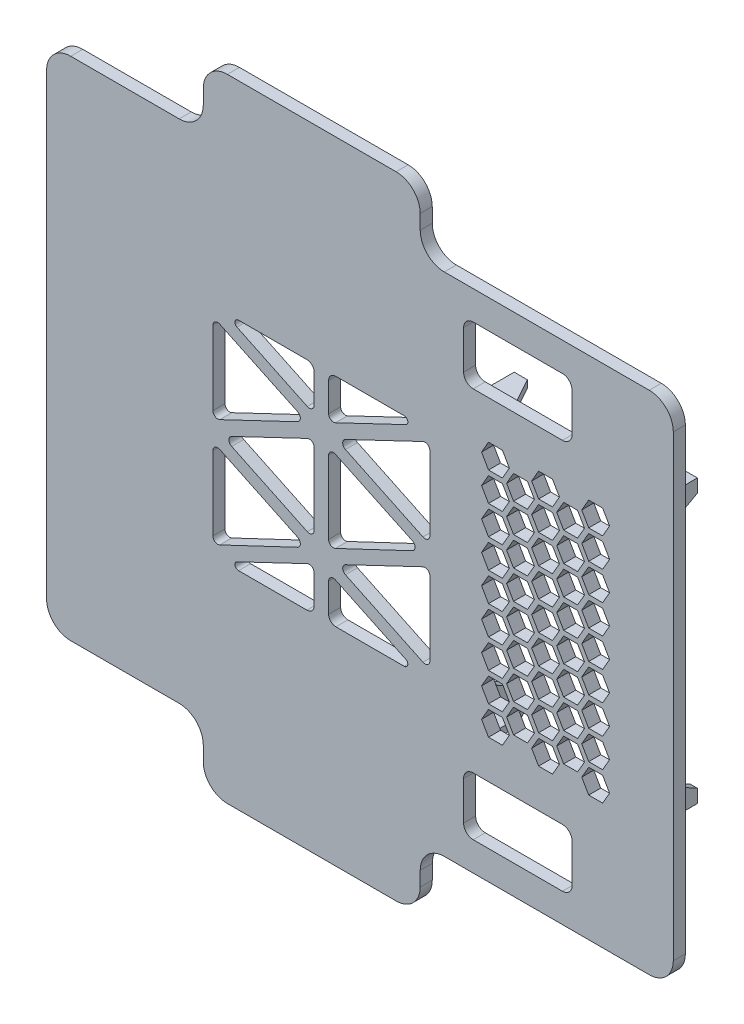
SolidWorks part; units mm, degrees
ref_plane "前视基准面" through (0, 0, 0) normal (0, 0, 1) x (1, 0, 0)
ref_plane "上视基准面" through (0, 0, 0) normal (0, 1, 0) x (1, 0, 0)
ref_plane "右视基准面" through (0, 0, 0) normal (1, 0, 0) x (0, 0, -1)
sketch "草图1" plane through (0, 0, 0) normal (0, 0, 1) x (1, 0, 0)
  line L2 (-130, 95) -> (-130, -95)
  line L3 (-120, -105) -> (-75, -105)
  line L4 (130, 95) -> (130, -95)
  line L5 (126.7518, 102.3765) -> (130, 105) construction
  line L6 (-130, -105) -> (-126.7518, -102.3765) construction
  line L9 (-65, -115) -> (-65, -121)
  line L10 (-55, -131) -> (15, -131)
  line L11 (25, -121) -> (25, -115)
  line L13 (35, -105) -> (120, -105)
  line L14 (126.7518, -102.3765) -> (130, -105) construction
  line L15 (-130, 105) -> (-126.7518, 102.3765) construction
  line L16 (-130, 0) -> (130, 0) construction
  line L17 (35, 105) -> (120, 105)
  line L18 (25, 121) -> (25, 115)
  line L19 (-55, 131) -> (15, 131)
  line L20 (-65, 115) -> (-65, 121)
  line L21 (-120, 105) -> (-75, 105)
  arc A1 (-120, -105) -> (-130, -95) centre (-120, -95) cw
  arc A3 (120, -105) -> (130, -95) centre (120, -95) ccw
  arc A8 (-65, -115) -> (-75, -105) centre (-75, -115) ccw
  arc A9 (25, -115) -> (35, -105) centre (35, -115) cw
  arc A10 (-55, -131) -> (-65, -121) centre (-55, -121) cw
  arc A11 (15, -131) -> (25, -121) centre (15, -121) ccw
  arc A12 (15, 131) -> (25, 121) centre (15, 121) cw
  arc A13 (-55, 131) -> (-65, 121) centre (-55, 121) ccw
  arc A14 (25, 115) -> (35, 105) centre (35, 115) ccw
  arc A15 (-65, 115) -> (-75, 105) centre (-75, 115) cw
  arc A16 (120, 105) -> (130, 95) centre (120, 95) cw
  arc A17 (-120, 105) -> (-130, 95) centre (-120, 95) ccw
  point P0 (0, 0)
  point P40 (25, -105)
  point P45 (25, 105)
  dimension "D2" = 10
  dimension "D3" = 65
  dimension "D4" = 10
  dimension "D5" = 105
  dimension "D7" = 10
  dimension "D8" = 10
  dimension "D10" = 10
  dimension "D12" = 10
  dimension "D13" = 105
  dimension "D18" = 90
  dimension "D19" = 6
extrude "凸台-拉伸1" add sketch "草图1" along normal blind 5
sketch "草图4" plane through (0, 0, 0) normal (0, 0, -1) x (-1, 0, 0)
  line L0 (-39, -47.5) -> (-39, -58.5)
  line L1 (-39, -58.5) -> (-50, -58.5)
  line L2 (-50, -58.5) -> (-50, -55.5)
  line L3 (-50, -55.5) -> (-42, -55.5)
  line L4 (-42, -55.5) -> (-42, -47.5)
  line L5 (-42, -47.5) -> (-39, -47.5)
  line L6 (-130, 0) -> (-25.5592, 0) construction
  line L7 (-130, -95) -> (-130, 95) construction
  line L10 (-130, -95) -> (-130, 95) construction
  dimension "D1" = 11
  dimension "D2" = 11
  dimension "D3" = 3
  dimension "D4" = 3
  dimension "D5" = 80
  dimension "D7" = 55.5
extrude "凸台-拉伸2" add sketch "草图4" along normal blind 20
sketch "草图5" plane through (0, -58.5, 0) normal (0, -1, 0) x (1, 0, 0)
  line L0 (50, -10) -> (44.5, -20)
  line L1 (50, -20) -> (50, 0) construction
  line L2 (50, -20) -> (39, -20) construction
  line L3 (44.5, -20) -> (50, -20)
  line L4 (50, -20) -> (50, -10)
  dimension "D1" = 10
  dimension "D2" = 5.5
extrude "切除-拉伸3" cut sketch "草图5" against normal blind 10
sketch "草图6" plane through (39, 0, 0) normal (-1, 0, 0) x (0, 0, 1)
  line L0 (-20, -53) -> (-10, -47.5)
  line L1 (-20, -58.5) -> (-20, -47.5) construction
  line L2 (-20, -47.5) -> (0, -47.5) construction
  line L3 (-10, -47.5) -> (-20, -47.5)
  line L4 (-20, -47.5) -> (-20, -53)
  dimension "D1" = 10
  dimension "D2" = 5.5
extrude "切除-拉伸4" cut sketch "草图6" against normal blind 10
ref_plane "基准面2" through (77, 0, 0) normal (1, 0, 0) x (0, 0, -1)
mirror "镜向1" about plane through (77, 0, 0) normal (1, 0, 0) of "凸台-拉伸2", "切除-拉伸4", "切除-拉伸3"
mirror "镜向2" about plane through (0, 0, 0) normal (0, 1, 0) of "镜向1"
sketch "草图7" plane through (0, 0, 0) normal (0, 0, -1) x (-1, 0, 0)
  line L4 (-112, -55.5) -> (-104, -55.5) construction
  line L5 (-112, 47.5) -> (-112, 55.5) construction
  line L6 (-112, 55.5) -> (-104, 55.5) construction
  line L7 (-92.013, 36) -> (-94.8997, 41)
  line L8 (-94.8997, 41) -> (-100.6732, 41)
  line L9 (-100.6732, 41) -> (-103.56, 36)
  line L10 (-103.56, 36) -> (-100.6732, 31)
  line L11 (-100.6732, 31) -> (-94.8997, 31)
  line L12 (-94.8997, 31) -> (-92.013, 36)
  line L13 (-77.0019, 36) -> (-97.7865, 36) construction
  line L14 (-74.1151, 31) -> (-71.2284, 36)
  line L15 (-71.2284, 36) -> (-74.1151, 41)
  line L16 (-74.1151, 41) -> (-79.8886, 41)
  line L17 (-79.8886, 41) -> (-82.7754, 36)
  line L18 (-82.7754, 36) -> (-79.8886, 31)
  line L19 (-79.8886, 31) -> (-74.1151, 31)
  line L20 (-92.013, 24) -> (-94.8997, 29)
  line L21 (-93.1677, 30) -> (-90.2809, 25)
  line L22 (-90.2809, 25) -> (-84.5074, 25)
  line L23 (-84.5074, 25) -> (-81.6207, 30)
  line L24 (-81.6207, 30) -> (-84.5074, 35)
  line L25 (-84.5074, 35) -> (-90.2809, 35)
  line L26 (-90.2809, 35) -> (-93.1677, 30)
  line L27 (-84.5074, 37) -> (-81.6207, 42)
  line L28 (-81.6207, 42) -> (-84.5074, 47)
  line L29 (-84.5074, 47) -> (-90.2809, 47)
  line L30 (-90.2809, 47) -> (-93.1677, 42)
  line L31 (-93.1677, 42) -> (-90.2809, 37)
  line L32 (-90.2809, 37) -> (-84.5074, 37)
  line L33 (-79.8886, 43) -> (-74.1151, 43)
  line L34 (-74.1151, 43) -> (-71.2284, 48)
  line L35 (-71.2284, 48) -> (-74.1151, 53)
  line L36 (-74.1151, 53) -> (-79.8886, 53)
  line L37 (-79.8886, 53) -> (-82.7754, 48)
  line L38 (-82.7754, 48) -> (-79.8886, 43)
  line L39 (-94.8997, 43) -> (-92.013, 48)
  line L40 (-92.013, 48) -> (-94.8997, 53)
  line L41 (-94.8997, 53) -> (-100.6732, 53)
  line L42 (-100.6732, 53) -> (-103.56, 48)
  line L43 (-103.56, 48) -> (-100.6732, 43)
  line L44 (-100.6732, 43) -> (-94.8997, 43)
  line L45 (-72.3831, 42) -> (-69.4963, 37)
  line L46 (-69.4963, 37) -> (-63.7228, 37)
  line L47 (-63.7228, 37) -> (-60.8361, 42)
  line L48 (-60.8361, 42) -> (-63.7228, 47)
  line L49 (-63.7228, 47) -> (-69.4963, 47)
  line L50 (-69.4963, 47) -> (-72.3831, 42)
  line L51 (-94.8997, 29) -> (-100.6732, 29)
  line L52 (-100.6732, 29) -> (-103.56, 24)
  line L53 (-103.56, 24) -> (-100.6732, 19)
  line L54 (-100.6732, 19) -> (-94.8997, 19)
  line L55 (-94.8997, 19) -> (-92.013, 24)
  line L56 (-93.1677, 18) -> (-90.2809, 13)
  line L57 (-90.2809, 13) -> (-84.5074, 13)
  line L58 (-84.5074, 13) -> (-81.6207, 18)
  line L59 (-81.6207, 18) -> (-84.5074, 23)
  line L60 (-84.5074, 23) -> (-90.2809, 23)
  line L61 (-90.2809, 23) -> (-93.1677, 18)
  line L62 (-74.1151, 19) -> (-71.2284, 24)
  line L63 (-71.2284, 24) -> (-74.1151, 29)
  line L64 (-74.1151, 29) -> (-79.8886, 29)
  line L65 (-79.8886, 29) -> (-82.7754, 24)
  line L66 (-82.7754, 24) -> (-79.8886, 19)
  line L67 (-79.8886, 19) -> (-74.1151, 19)
  line L68 (-72.3831, 30) -> (-69.4963, 25)
  line L69 (-69.4963, 25) -> (-63.7228, 25)
  line L70 (-63.7228, 25) -> (-60.8361, 30)
  line L71 (-60.8361, 30) -> (-63.7228, 35)
  line L72 (-63.7228, 35) -> (-69.4963, 35)
  line L73 (-69.4963, 35) -> (-72.3831, 30)
  line L74 (-92.013, 12) -> (-94.8997, 17)
  line L75 (-94.8997, 17) -> (-100.6732, 17)
  line L76 (-100.6732, 17) -> (-103.56, 12)
  line L77 (-103.56, 12) -> (-100.6732, 7)
  line L78 (-100.6732, 7) -> (-94.8997, 7)
  line L79 (-94.8997, 7) -> (-92.013, 12)
  line L80 (-93.1677, 6) -> (-90.2809, 1)
  line L81 (-90.2809, 1) -> (-84.5074, 1)
  line L82 (-84.5074, 1) -> (-81.6207, 6)
  line L83 (-81.6207, 6) -> (-84.5074, 11)
  line L84 (-84.5074, 11) -> (-90.2809, 11)
  line L85 (-90.2809, 11) -> (-93.1677, 6)
  line L86 (-74.1151, 7) -> (-71.2284, 12)
  line L87 (-71.2284, 12) -> (-74.1151, 17)
  line L88 (-74.1151, 17) -> (-79.8886, 17)
  line L89 (-79.8886, 17) -> (-82.7754, 12)
  line L90 (-82.7754, 12) -> (-79.8886, 7)
  line L91 (-79.8886, 7) -> (-74.1151, 7)
  line L92 (-72.3831, 18) -> (-69.4963, 13)
  line L93 (-69.4963, 13) -> (-63.7228, 13)
  line L94 (-63.7228, 13) -> (-60.8361, 18)
  line L95 (-60.8361, 18) -> (-63.7228, 23)
  line L96 (-63.7228, 23) -> (-69.4963, 23)
  line L97 (-69.4963, 23) -> (-72.3831, 18)
  line L98 (-92.013, 0) -> (-94.8997, 5)
  line L99 (-94.8997, 5) -> (-100.6732, 5)
  line L100 (-100.6732, 5) -> (-103.56, 0)
  line L101 (-103.56, 0) -> (-100.6732, -5)
  line L102 (-100.6732, -5) -> (-94.8997, -5)
  line L103 (-94.8997, -5) -> (-92.013, 0)
  line L104 (-93.1677, -6) -> (-90.2809, -11)
  line L105 (-90.2809, -11) -> (-84.5074, -11)
  line L106 (-84.5074, -11) -> (-81.6207, -6)
  line L107 (-81.6207, -6) -> (-84.5074, -1)
  line L108 (-84.5074, -1) -> (-90.2809, -1)
  line L109 (-90.2809, -1) -> (-93.1677, -6)
  line L110 (-74.1151, -5) -> (-71.2284, 0)
  line L111 (-71.2284, 0) -> (-74.1151, 5)
  line L112 (-74.1151, 5) -> (-79.8886, 5)
  line L113 (-79.8886, 5) -> (-82.7754, 0)
  line L114 (-82.7754, 0) -> (-79.8886, -5)
  line L115 (-79.8886, -5) -> (-74.1151, -5)
  line L116 (-72.3831, 6) -> (-69.4963, 1)
  line L117 (-69.4963, 1) -> (-63.7228, 1)
  line L118 (-63.7228, 1) -> (-60.8361, 6)
  line L119 (-60.8361, 6) -> (-63.7228, 11)
  line L120 (-63.7228, 11) -> (-69.4963, 11)
  line L121 (-69.4963, 11) -> (-72.3831, 6)
  line L122 (-92.013, -12) -> (-94.8997, -7)
  line L123 (-94.8997, -7) -> (-100.6732, -7)
  line L124 (-100.6732, -7) -> (-103.56, -12)
  line L125 (-103.56, -12) -> (-100.6732, -17)
  line L126 (-100.6732, -17) -> (-94.8997, -17)
  line L127 (-94.8997, -17) -> (-92.013, -12)
  line L128 (-93.1677, -18) -> (-90.2809, -23)
  line L129 (-90.2809, -23) -> (-84.5074, -23)
  line L130 (-84.5074, -23) -> (-81.6207, -18)
  line L131 (-81.6207, -18) -> (-84.5074, -13)
  line L132 (-84.5074, -13) -> (-90.2809, -13)
  line L133 (-90.2809, -13) -> (-93.1677, -18)
  line L134 (-74.1151, -17) -> (-71.2284, -12)
  line L135 (-71.2284, -12) -> (-74.1151, -7)
  line L136 (-74.1151, -7) -> (-79.8886, -7)
  line L137 (-79.8886, -7) -> (-82.7754, -12)
  line L138 (-82.7754, -12) -> (-79.8886, -17)
  line L139 (-79.8886, -17) -> (-74.1151, -17)
  line L140 (-72.3831, -6) -> (-69.4963, -11)
  line L141 (-69.4963, -11) -> (-63.7228, -11)
  line L142 (-63.7228, -11) -> (-60.8361, -6)
  line L143 (-60.8361, -6) -> (-63.7228, -1)
  line L144 (-63.7228, -1) -> (-69.4963, -1)
  line L145 (-69.4963, -1) -> (-72.3831, -6)
  line L146 (-92.013, -24) -> (-94.8997, -19)
  line L147 (-94.8997, -19) -> (-100.6732, -19)
  line L148 (-100.6732, -19) -> (-103.56, -24)
  line L149 (-103.56, -24) -> (-100.6732, -29)
  line L150 (-100.6732, -29) -> (-94.8997, -29)
  line L151 (-94.8997, -29) -> (-92.013, -24)
  line L152 (-93.1677, -30) -> (-90.2809, -35)
  line L153 (-90.2809, -35) -> (-84.5074, -35)
  line L154 (-84.5074, -35) -> (-81.6207, -30)
  line L155 (-81.6207, -30) -> (-84.5074, -25)
  line L156 (-84.5074, -25) -> (-90.2809, -25)
  line L157 (-90.2809, -25) -> (-93.1677, -30)
  line L158 (-74.1151, -29) -> (-71.2284, -24)
  line L159 (-71.2284, -24) -> (-74.1151, -19)
  line L160 (-74.1151, -19) -> (-79.8886, -19)
  line L161 (-79.8886, -19) -> (-82.7754, -24)
  line L162 (-82.7754, -24) -> (-79.8886, -29)
  line L163 (-79.8886, -29) -> (-74.1151, -29)
  line L164 (-72.3831, -18) -> (-69.4963, -23)
  line L165 (-69.4963, -23) -> (-63.7228, -23)
  line L166 (-63.7228, -23) -> (-60.8361, -18)
  line L167 (-60.8361, -18) -> (-63.7228, -13)
  line L168 (-63.7228, -13) -> (-69.4963, -13)
  line L169 (-69.4963, -13) -> (-72.3831, -18)
  line L170 (-92.013, -36) -> (-94.8997, -31)
  line L171 (-94.8997, -31) -> (-100.6732, -31)
  line L172 (-100.6732, -31) -> (-103.56, -36)
  line L173 (-103.56, -36) -> (-100.6732, -41)
  line L174 (-100.6732, -41) -> (-94.8997, -41)
  line L175 (-94.8997, -41) -> (-92.013, -36)
  line L176 (-93.1677, -42) -> (-90.2809, -47)
  line L177 (-90.2809, -47) -> (-84.5074, -47)
  line L178 (-84.5074, -47) -> (-81.6207, -42)
  line L179 (-81.6207, -42) -> (-84.5074, -37)
  line L180 (-84.5074, -37) -> (-90.2809, -37)
  line L181 (-90.2809, -37) -> (-93.1677, -42)
  line L182 (-74.1151, -41) -> (-71.2284, -36)
  line L183 (-71.2284, -36) -> (-74.1151, -31)
  line L184 (-74.1151, -31) -> (-79.8886, -31)
  line L185 (-79.8886, -31) -> (-82.7754, -36)
  line L186 (-82.7754, -36) -> (-79.8886, -41)
  line L187 (-79.8886, -41) -> (-74.1151, -41)
  line L188 (-72.3831, -30) -> (-69.4963, -35)
  line L189 (-69.4963, -35) -> (-63.7228, -35)
  line L190 (-63.7228, -35) -> (-60.8361, -30)
  line L191 (-60.8361, -30) -> (-63.7228, -25)
  line L192 (-63.7228, -25) -> (-69.4963, -25)
  line L193 (-69.4963, -25) -> (-72.3831, -30)
  line L194 (-92.013, -48) -> (-94.8997, -43)
  line L195 (-94.8997, -43) -> (-100.6732, -43)
  line L196 (-100.6732, -43) -> (-103.56, -48)
  line L197 (-103.56, -48) -> (-100.6732, -53)
  line L198 (-100.6732, -53) -> (-94.8997, -53)
  line L199 (-94.8997, -53) -> (-92.013, -48)
  line L206 (-74.1151, -53) -> (-71.2284, -48)
  line L207 (-71.2284, -48) -> (-74.1151, -43)
  line L208 (-74.1151, -43) -> (-79.8886, -43)
  line L209 (-79.8886, -43) -> (-82.7754, -48)
  line L210 (-82.7754, -48) -> (-79.8886, -53)
  line L211 (-79.8886, -53) -> (-74.1151, -53)
  line L212 (-72.3831, -42) -> (-69.4963, -47)
  line L213 (-69.4963, -47) -> (-63.7228, -47)
  line L214 (-63.7228, -47) -> (-60.8361, -42)
  line L215 (-60.8361, -42) -> (-63.7228, -37)
  line L216 (-63.7228, -37) -> (-69.4963, -37)
  line L217 (-69.4963, -37) -> (-72.3831, -42)
  line L218 (-61.9908, 36) -> (-59.104, 31)
  line L219 (-61.9908, 48) -> (-59.104, 43)
  line L220 (-59.104, 43) -> (-53.3305, 43)
  line L221 (-53.3305, 43) -> (-50.4438, 48)
  line L222 (-50.4438, 48) -> (-53.3305, 53)
  line L223 (-53.3305, 53) -> (-59.104, 53)
  line L224 (-59.104, 53) -> (-61.9908, 48)
  line L225 (-59.104, 31) -> (-53.3305, 31)
  line L226 (-53.3305, 31) -> (-50.4438, 36)
  line L227 (-50.4438, 36) -> (-53.3305, 41)
  line L228 (-53.3305, 41) -> (-59.104, 41)
  line L229 (-59.104, 41) -> (-61.9908, 36)
  line L230 (-61.9908, 24) -> (-59.104, 19)
  line L231 (-59.104, 19) -> (-53.3305, 19)
  line L232 (-53.3305, 19) -> (-50.4438, 24)
  line L233 (-50.4438, 24) -> (-53.3305, 29)
  line L234 (-53.3305, 29) -> (-59.104, 29)
  line L235 (-59.104, 29) -> (-61.9908, 24)
  line L236 (-61.9908, 12) -> (-59.104, 7)
  line L237 (-59.104, 7) -> (-53.3305, 7)
  line L238 (-53.3305, 7) -> (-50.4438, 12)
  line L239 (-50.4438, 12) -> (-53.3305, 17)
  line L240 (-53.3305, 17) -> (-59.104, 17)
  line L241 (-59.104, 17) -> (-61.9908, 12)
  line L242 (-61.9908, 0) -> (-59.104, -5)
  line L243 (-59.104, -5) -> (-53.3305, -5)
  line L244 (-53.3305, -5) -> (-50.4438, 0)
  line L245 (-50.4438, 0) -> (-53.3305, 5)
  line L246 (-53.3305, 5) -> (-59.104, 5)
  line L247 (-59.104, 5) -> (-61.9908, 0)
  line L248 (-61.9908, -12) -> (-59.104, -17)
  line L249 (-59.104, -17) -> (-53.3305, -17)
  line L250 (-53.3305, -17) -> (-50.4438, -12)
  line L251 (-50.4438, -12) -> (-53.3305, -7)
  line L252 (-53.3305, -7) -> (-59.104, -7)
  line L253 (-59.104, -7) -> (-61.9908, -12)
  line L254 (-61.9908, -24) -> (-59.104, -29)
  line L255 (-59.104, -29) -> (-53.3305, -29)
  line L256 (-53.3305, -29) -> (-50.4438, -24)
  line L257 (-50.4438, -24) -> (-53.3305, -19)
  line L258 (-53.3305, -19) -> (-59.104, -19)
  line L259 (-59.104, -19) -> (-61.9908, -24)
  line L260 (-61.9908, -36) -> (-59.104, -41)
  line L261 (-59.104, -41) -> (-53.3305, -41)
  line L262 (-53.3305, -41) -> (-50.4438, -36)
  line L263 (-50.4438, -36) -> (-53.3305, -31)
  line L264 (-53.3305, -31) -> (-59.104, -31)
  line L265 (-59.104, -31) -> (-61.9908, -36)
  line L266 (-61.9908, -48) -> (-59.104, -53)
  line L267 (-59.104, -53) -> (-53.3305, -53)
  line L268 (-53.3305, -53) -> (-50.4438, -48)
  line L269 (-50.4438, -48) -> (-53.3305, -43)
  line L270 (-53.3305, -43) -> (-59.104, -43)
  line L271 (-59.104, -43) -> (-61.9908, -48)
  line L272 (-93.1677, -54) -> (-90.2809, -59) [skipped]
  line L273 (-90.2809, -59) -> (-84.5074, -59) [skipped]
  line L274 (-84.5074, -59) -> (-81.6207, -54) [skipped]
  line L275 (-81.6207, -54) -> (-84.5074, -49) [skipped]
  line L276 (-84.5074, -49) -> (-90.2809, -49) [skipped]
  line L277 (-90.2809, -49) -> (-93.1677, -54) [skipped]
  circle A0 centre (-97.7865, 36) radius 5 construction
  circle A1 centre (-77.0019, 36) radius 5 construction
  circle A2 centre (-87.3942, 30) radius 5 construction
  circle A3 centre (-87.3942, 42) radius 5 construction
  circle A4 centre (-77.0019, 48) radius 5 construction
  circle A5 centre (-97.7865, 48) radius 5 construction
  circle A6 centre (-66.6096, 42) radius 5 construction
  circle A7 centre (-56.2173, 48) radius 5 construction
  point P4 (-87.3942, 37)
  dimension "D1" = 2
  dimension "D3" = 10
  dimension "D4" = 10
  dimension "D5" = 2
  dimension "D7" = 10
  dimension "D11" = 10
  dimension "D14" = 10
  dimension "D15" = 10
  dimension "D20" = 10
  dimension "D2" = 2
  dimension "D6" = 2
  dimension "D8" = 2
  dimension "D9" = 2
  dimension "D10" = 2
  dimension "D12" = 2
  dimension "D13" = 2
  dimension "D16" = 2
  dimension "D17" = 2
  dimension "D19" = 2
  dimension "D21" = 9
  dimension "D22" = 2.5
  dimension "D23" = 2.5
  dimension "D24" = 8.44
  dimension "D18" = 8
extrude "切除-拉伸5" cut sketch "草图7" against normal blind 5
sketch "草图8" plane through (0, 0, 0) normal (0, 0, -1) x (-1, 0, 0)
  line L0 (-75.3677, 120) -> (-75.3677, -120)
  line L1 (-100.0285, 77.2863) -> (-100.0285, -77.2863)
  line L2 (-100.0285, 77.2863) -> (-75.3677, 120)
  line L3 (-100.0285, -77.2863) -> (-75.3677, -120)
  line L4 (-37.1297, 0) -> (-146.8562, 0) construction
  dimension "D1" = 30
  dimension "D2" = 30
  dimension "D3" = 120
  dimension "D4" = 120
sketch "草图9" plane through (0, 0, 0) normal (0, 0, -1) x (-1, 0, 0)
  line L0 (148.8518, 0) -> (-37.1297, 0) construction
  line L1 (-29, 41) -> (-29, 4)
  line L2 (-25, -45) -> (13, -45)
  line L3 (61, -41) -> (61, -4)
  line L4 (57, 45) -> (19, 45)
  line L14 (-29, 41) -> (9.8049, 22.5)
  line L15 (57, 0) -> (19, -18.1163)
  line L16 (130, 95) -> (130, -95) construction
  line L17 (63, 93) -> (118, 93)
  line L18 (63, 93) -> (63, 66)
  line L19 (63, 66) -> (118, 66)
  line L20 (118, 93) -> (118, 66)
  line L21 (75, 105) -> (120, 105) construction
  line L22 (63, -66) -> (118, -66)
  line L23 (118, -93) -> (118, -66)
  line L24 (63, -93) -> (118, -93)
  line L25 (63, -93) -> (63, -66)
  line L26 (-120, 105) -> (-35, 105) construction
  line L27 (-43, 93) -> (-88, 93)
  line L28 (-43, 93) -> (-43, 69)
  line L29 (-43, 69) -> (-88, 69)
  line L30 (-88, 93) -> (-88, 69)
  line L31 (-130, -95) -> (-130, 95) construction
  line L32 (-43, -69) -> (-88, -69)
  line L33 (-88, -93) -> (-88, -69)
  line L34 (-43, -93) -> (-88, -93)
  line L35 (-43, -93) -> (-43, -69)
  line L36 (-25, 45) -> (13, 26.8837)
  line L37 (-25, -45) -> (13, -26.8837)
  line L38 (61, 41) -> (22.0746, 22.5575)
  line L39 (-25.5359, 0) -> (13, -18.258)
  line L40 (57, 45) -> (19, 26.8837)
  line L41 (57, -45) -> (19, -26.8837)
  line L42 (16, 61.4977) -> (16, -60.5731) construction
  line L43 (13, 45) -> (13, 26.8837)
  line L44 (19, 45) -> (19, 26.8837)
  line L45 (13, 18.258) -> (13, -18.258)
  line L46 (9.8049, 22.5) -> (-29, 4)
  line L47 (19, 18.1163) -> (57, 0)
  line L48 (22.0746, 22.5575) -> (61, 4)
  line L49 (13, 18.258) -> (-25.5359, 0)
  line L50 (19, 18.1163) -> (19, -18.1163)
  line L51 (22.0746, -22.5575) -> (61, -41)
  line L52 (9.8049, -22.5) -> (-29, -41)
  line L53 (9.8049, -22.5) -> (-29, -4)
  line L54 (22.0746, -22.5575) -> (61, -4)
  line L55 (13, -26.8837) -> (13, -45)
  line L56 (19, -26.8837) -> (19, -45)
  line L57 (13, 45) -> (-25, 45)
  line L58 (-29, -4) -> (-29, -41)
  line L59 (19, -45) -> (57, -45)
  line L60 (61, 4) -> (61, 41)
  line L61 (-44, 41) -> (-44, -37.8122) construction
  dimension "D1" = 45
  dimension "D2" = 45
  dimension "D3" = 15
  dimension "D4" = 90
  dimension "D5" = 1
  dimension "D7" = 12
  dimension "D8" = 12
  dimension "D9" = 27
  dimension "D10" = 55
  dimension "D11" = 12
  dimension "D12" = 45
  dimension "D13" = 42
  dimension "D14" = 24
  dimension "D21" = 4
  dimension "D22" = 4
  dimension "D23" = 4
  dimension "D24" = 4
  dimension "D26" = 4
  dimension "D27" = 3
  dimension "D28" = 45
extrude "切除-拉伸6" cut sketch "草图9" against normal blind 5 contours L27 L30 L29 L28 | L34 L35 L32 L33 | L4 L44 L40 | L48 L60 L38 | L47 L50 L15 | L54 L51 L3 | L56 L59 L41 | L55 L37 L2 | L53 L58 L52 | L45 L49 L39 | L46 L14 L1 | L43 L57 L36 | L57 L36 L43 region at (16.065, 22.5, 0) region at (-0.3333, -38.9612, 0) region at (-48.0249, -22.5192, 0) region at (-31.6667, 38.9612, 0) region at (-31.6667, 0, 0) region at (65.5, 81, 0) region at (65.5, -81, 0) region at (-0.3333, 38.9612, 0) region at (-48.0249, 22.5192, 0) region at (-0.1547, 0, 0) region at (-31.6667, -38.9612, 0) region at (16.065, -22.5, 0)
fillet "圆角1" radius 4 8 edges at (43, -93, 2.5) (88, -69, 2.5) (43, -69, 2.5) (88, -93, 2.5) (88, 69, 2.5) (43, 69, 2.5) (43, 93, 2.5) (88, 93, 2.5)
fillet "圆角2" radius 1.5 4 edges at (25, -45, 2.5) (-57, -45, 2.5) (25, 45, 2.5) (-57, 45, 2.5)
fillet "圆角3" radius 2 22 edges at (29, -4, 2.5) (29, 4, 2.5) (-13, -18.258, 2.5) (-61, -41, 2.5) (-61, 4, 2.5) (-13, -26.8837, 2.5) (-13, 18.258, 2.5) (-61, -4, 2.5) (-22.0746, -22.5575, 2.5) (25.5359, 0, 2.5) (-22.0746, 22.5575, 2.5) (-61, 41, 2.5) (-19, 26.8837, 2.5) (-19, -26.8837, 2.5) (-19, -18.1163, 2.5) (29, -41, 2.5) (29, 41, 2.5) (-57, 0, 2.5) (-9.8049, -22.5, 2.5) (-13, 26.8837, 2.5) (-9.8049, 22.5, 2.5) (-19, 18.1163, 2.5)
fillet "圆角4" radius 3 4 edges at (-13, -45, 2.5) (-13, 45, 2.5) (-19, -45, 2.5) (-19, 45, 2.5)
equation "\"45、\"=43.7672"
